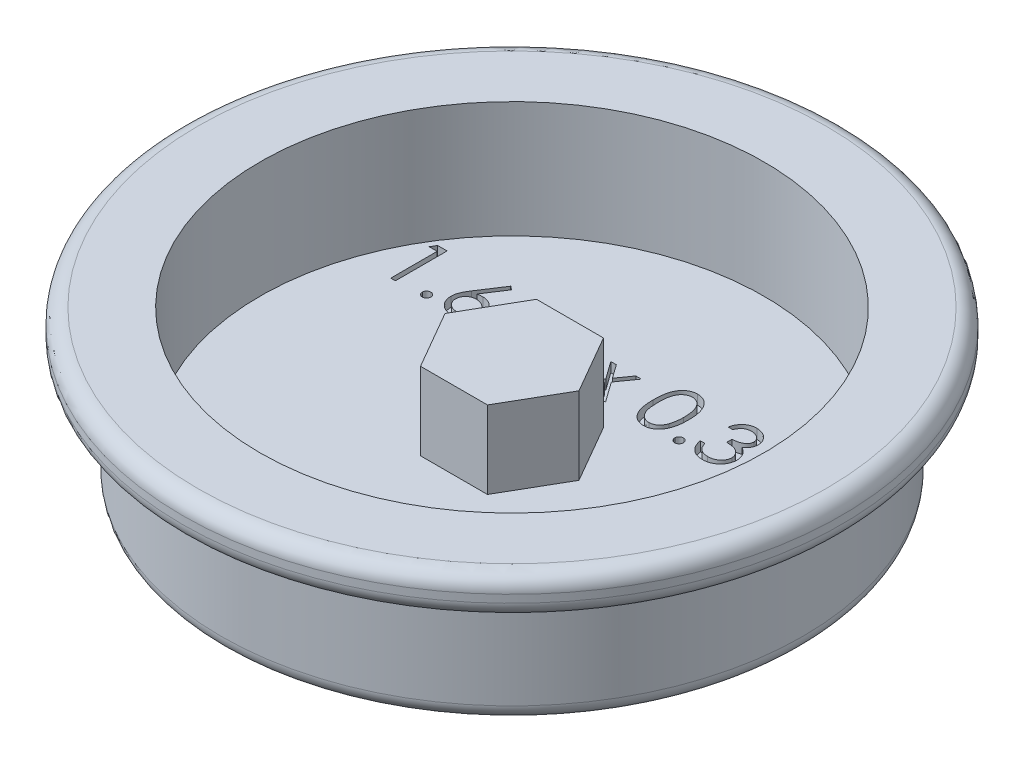
SolidWorks part; units mm, degrees
ref_plane "Front Plane" through (0, 0, 0) normal (0, 0, 1) x (1, 0, 0)
ref_plane "Top Plane" through (0, 0, 0) normal (0, 1, 0) x (1, 0, 0)
ref_plane "Right Plane" through (0, 0, 0) normal (1, 0, 0) x (0, 0, -1)
sketch "Sketch1" plane through (0, 0, 0) normal (0, 0, 1) x (1, 0, 0)
  line L0 (0, 0) -> (22.5425, 0)
  line L1 (23.8125, 1.27) -> (23.8125, 8.255)
  line L2 (25.0825, 9.525) -> (25.7175, 9.525)
  line L3 (26.9875, 10.795) -> (26.9875, 11.43)
  line L4 (25.7175, 12.7) -> (20.6375, 12.7)
  line L5 (20.6375, 12.7) -> (20.6375, 3.175)
  line L6 (20.6375, 3.175) -> (0, 3.175)
  line L7 (0, 3.175) -> (0, 0)
  arc A0 (26.9875, 11.43) -> (25.7175, 12.7) centre (25.7175, 11.43) ccw
  arc A1 (25.7175, 9.525) -> (26.9875, 10.795) centre (25.7175, 10.795) ccw
  arc A2 (23.8125, 8.255) -> (25.0825, 9.525) centre (25.0825, 8.255) cw
  arc A3 (22.5425, 0) -> (23.8125, 1.27) centre (22.5425, 1.27) ccw
  point P3 (0, 1.5875)
  dimension "D7" = 1.27
  dimension "D1" = 3.175
  dimension "D2" = 3.175
  dimension "D3" = 3.175
  dimension "D4" = 6.35
  dimension "D5" = 20.6375
  dimension "D6" = 9.525
revolve "Revolve1" add sketch "Sketch1" angle 360 about L7
sketch "Sketch2" plane through (0, 3.175, 0) normal (0, 1, 0) x (1, 0, 0)
  line L1 (2.7423, 4.7498) -> (-2.7423, 4.7498)
  line L2 (-2.7423, 4.7498) -> (-5.4846, 0)
  line L3 (-5.4846, 0) -> (-2.7423, -4.7498)
  line L4 (-2.7423, -4.7498) -> (2.7423, -4.7498)
  line L5 (2.7423, -4.7498) -> (5.4846, 0)
  line L6 (5.4846, 0) -> (2.7423, 4.7498)
  circle A0 centre (0, 0) radius 4.7498 construction
  dimension "D1" = 9.4996
extrude "Boss-Extrude1" add sketch "Sketch2" along normal blind 6.35
sketch "Sketch3" plane through (0, 3.175, 0) normal (0, 1, 0) x (1, 0, 0)
  text T0 "1.625 x 0.375" font "Century Gothic" height in points 16
  point P1 (-18.0267, 6.635)
extrude "Cut-Extrude1" cut sketch "Sketch3" against normal blind 0.7937
